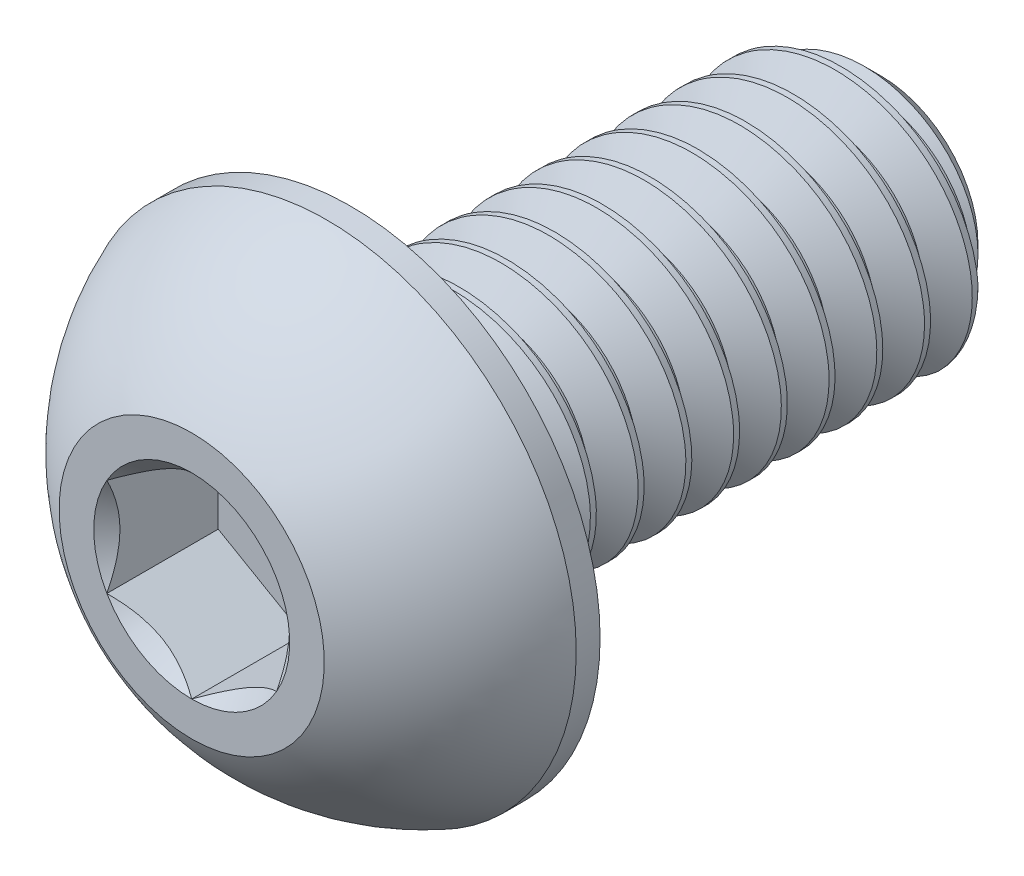
SolidWorks part; units mm, degrees
material "AISI 316 Annealed Stainless Steel Bar (SS)"
ref_plane "Front" through (0, 0, 0) normal (0, 0, 1) x (1, 0, 0)
ref_plane "Top" through (0, 0, 0) normal (0, 1, 0) x (1, 0, 0)
ref_plane "Right" through (0, 0, 0) normal (1, 0, 0) x (0, 0, -1)
sketch "Sketch1" plane through (0, 0, 0) normal (1, 0, 0) x (0, 0, -1)
  line L2 (1.5, 1.25) -> (6.5, 1.25)
  line L3 (6.5, 1.25) -> (6.5, 0)
  line L4 (6.5, 0) -> (1.5, 0)
  line L6 (1.275, 2.35) -> (1.5, 2.35) construction
  line L7 (6.5, 1.25) -> (6.5, -1.25) construction
  line L8 (0, 0) -> (1.5, 0) construction
  line L9 (1.5, 2.35) -> (1.5, -2.35) construction
  line L11 (1.5, 1.25) -> (1.5, 0)
  line L13 (0, 0.8) -> (0, -0.8) construction
  line L14 (0, 0.8) -> (0, 1.25) construction
  arc A3 (0, 1.25) -> (1.275, 2.35) centre (2.1904, 0) cw construction
  dimension "D1" = 0.225
revolve "Revolve1" add sketch "Sketch1" angle 360 mid plane about L4
sketch "Sketch3" plane through (0, 0, -6.5) normal (0, 0, -1) x (-1, 0, 0)
  circle A0 centre (0, 0) radius 1.25
curve "Helix/Spiral1" pitch 0.45 height 5.45 radius 1.25 centre (0, 0, -6.5) axis (0, 0, 1) start towards (0, 1, 0)
sketch "Sketch2" plane through (0, 0, 0) normal (1, 0, 0) x (0, 0, -1)
  line L0 (6.5, 1.25) -> (6.8937, 1.25)
  line L1 (6.8937, 1.25) -> (6.725, 0.9577)
  line L2 (6.725, 0.9577) -> (6.6688, 0.9577)
  line L3 (6.6688, 0.9577) -> (6.5, 1.25)
  line L4 (6.5844, 1.1039) -> (6.8094, 1.1039) construction
  dimension "D1" = 60
  dimension "D2" = 0.0563
  dimension "D3" = 0.225
chamfer "Chamfer1" distance 0.3375 angle 45 1 edges at (0, 1.25, -6.5)
sweep "Cut-Sweep1" cut profiles "Sketch2" path "Helix/Spiral1" align with end faces yes
sketch "Sketch7" plane through (0, 0, 0) normal (1, 0, 0) x (0, 0, -1)
  line L6 (1.275, 2.35) -> (1.5, 2.35) construction
  line L8 (0, 0) -> (1.5, 0) construction
  line L11 (1.5, 2.35) -> (1.5, -2.35) construction
  line L12 (1.275, 2.35) -> (1.5, 2.35)
  line L13 (0, 0) -> (1.5, 0)
  line L14 (0, 0.8) -> (0, -0.8) construction
  line L15 (1.5, 2.35) -> (1.5, 0)
  line L16 (0, 1.25) -> (0, 0)
  arc A2 (1.275, 2.35) -> (0, 1.25) centre (2.1904, 0) ccw construction
  arc A3 (1.275, 2.35) -> (0, 1.25) centre (2.1904, 0) ccw
revolve "Revolve2" add sketch "Sketch7" angle 360 mid plane about L13
sketch "Sketch5" plane through (0, 0, 0) normal (0, 0, 1) x (1, 0, 0)
  line L1 (0.8, -0.4619) -> (0.8, 0.4619)
  line L2 (0.8, 0.4619) -> (0, 0.9238)
  line L3 (0, 0.9238) -> (-0.8, 0.4619)
  line L4 (-0.8, 0.4619) -> (-0.8, -0.4619)
  line L5 (-0.8, -0.4619) -> (0, -0.9238)
  line L6 (0, -0.9238) -> (0.8, -0.4619)
  circle A0 centre (0, 0) radius 0.8 construction
extrude "Cut-Extrude2" cut sketch "Sketch5" against normal blind 1.05
sketch "Sketch6" plane through (0, 0, 0) normal (0, 0, 1) x (1, 0, 0)
  circle A0 centre (0, 0) radius 0.9238
extrude "Cut-Extrude3" cut sketch "Sketch6" against normal blind 1.05 draft 45
sketch "Sketch9" [suppressed] plane through (0, 0, -6.6) normal (0, 0, 1) x (1, 0, 0)
  circle A2 centre (0, 0) radius 6
extrude "Boss-Extrude2" [suppressed] add sketch "Sketch9" against normal offset from surface (19 mm away) 32 up to face at (0, 0.9125, -6.5)
sketch "Sketch10" plane through (0, 0, 0) normal (1, 0, 0) x (0, 0, -1)
  line L0 (6.5, 1.25) -> (6.5, -1.25) construction
  point P0 (5.825, -1.25)
  dimension "D1" = 0.675
equation "\"D3@Helix/Spiral1\" = \"Lg@Sketch1\" + \"D4@Helix/Spiral1\""
equation "\"D2@Sketch2\" = \"D4@Helix/Spiral1\" * .125"
equation "\"D3@Sketch2\" = \"D4@Helix/Spiral1\" * .5"
equation "\"D1@Chamfer1\" = \"D4@Helix/Spiral1\" * .75"
equation "\"D1@Cut-Extrude2\" = \"Head Ht@Sketch1\" * .7"
equation "\"D1@Sketch1\" = \"Head Ht@Sketch1\" * .15"
equation "\"D1@Sketch10\" = \"D4@Helix/Spiral1\" * 1.5"
equation "\"D1@Cut-Extrude3\" = \"D1@Cut-Extrude2\""
